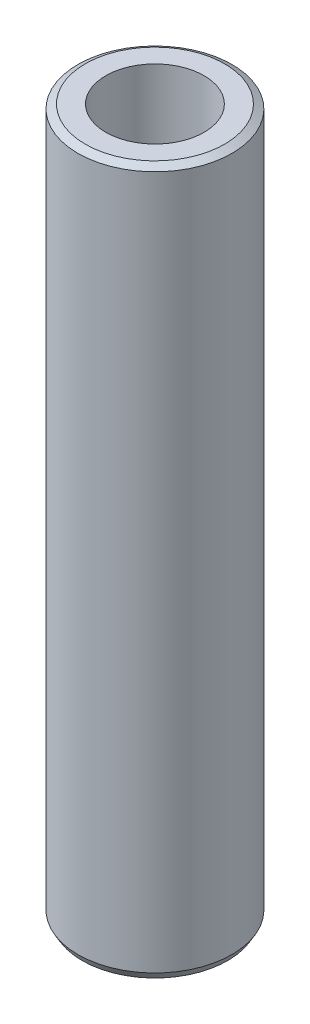
SolidWorks part; units mm, degrees
ref_plane "Front Plane" through (0, 0, 0) normal (0, 0, 1) x (1, 0, 0)
ref_plane "Top Plane" through (0, 0, 0) normal (0, 1, 0) x (1, 0, 0)
ref_plane "Right Plane" through (0, 0, 0) normal (1, 0, 0) x (0, 0, -1)
sketch "Sketch1" plane through (0, 0, 0) normal (0, 1, 0) x (1, 0, 0)
  circle A0 centre (0, 0) radius 50
  dimension "SHAFT_OD" = 100
extrude "Boss-Extrude1" add sketch "Sketch1" along normal blind 457.7994
sketch "Sketch2" plane through (0, 0, 0) normal (0, 1, 0) x (1, 0, 0)
  circle A0 centre (0, 0) radius 31.8719
  dimension "BORE_D" = 63.7437
extrude "Cut-Extrude1" cut sketch "Sketch2" along normal through all
chamfer "Chamfer1" distance 2.7624 angle 60 2 edges at (0, 457.7994, 50) (0, 0, 50) first distance on face at (0, 457.7994, 50) first distance on face at (0, 0, 31.8719)
